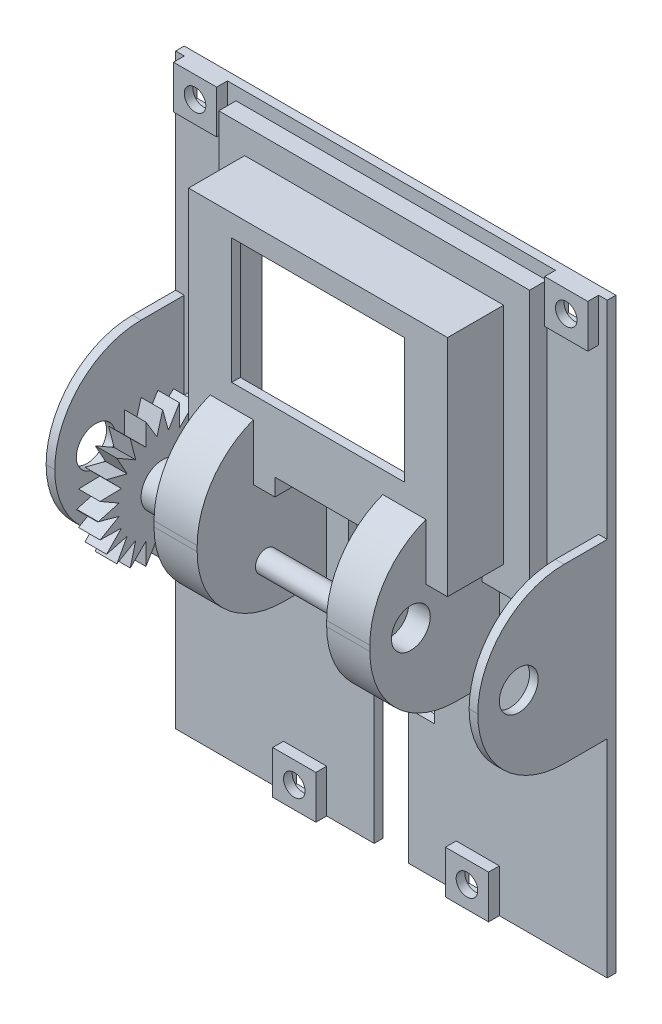
SolidWorks part; units mm, degrees
material "ABS"
ref_plane "Plan de face" through (0, 0, 0) normal (0, 0, 1) x (1, 0, 0)
ref_plane "Plan de dessus" through (0, 0, 0) normal (0, 1, 0) x (1, 0, 0)
ref_plane "Plan de droite" through (0, 0, 0) normal (1, 0, 0) x (0, 0, -1)
sketch "Esquisse1" plane through (0, 0, 0) normal (0, 0, 1) x (1, 0, 0)
  line L0 (0, 0) -> (0, 87) construction
  line L1 (-50, -68) -> (50, -68)
  line L2 (-50, -68) -> (-50, 68)
  line L3 (-50, 68) -> (50, 68)
  line L4 (50, -68) -> (50, 68)
  line L5 (-50, -68) -> (50, 68) construction
  line L6 (-50, 68) -> (50, -68) construction
  line L7 (-34, 3) -> (34, 3)
  line L8 (-34, 3) -> (-34, 63)
  line L9 (-34, 63) -> (34, 63)
  line L10 (34, 3) -> (34, 63)
  line L11 (0, 87) -> (0, -87) construction
  line L13 (-10, 3) -> (10, 3)
  line L14 (-10, 3) -> (-10, -37)
  line L15 (-10, -68) -> (10, -68)
  line L16 (10, 3) -> (10, -37)
  line L17 (-10, 3) -> (10, 3)
  line L18 (-10, 3) -> (-10, -37)
  line L19 (-10, -37) -> (10, -37)
  line L20 (10, 3) -> (10, -37)
  point P0 (0, 0)
  dimension "D1" = 136
  dimension "D2" = 100
  dimension "D3" = 68
  dimension "D4" = 60
  dimension "D5" = 16
  dimension "D6" = 5
  dimension "D7" = 174
  dimension "D8" = 87
  dimension "D9" = 20
  dimension "D10" = 24
  dimension "D11" = 40
extrude "Boss.-Extru.1" add sketch "Esquisse1" along normal blind 2 contours L1 L4 L3 L2 L19 L14 L7 L8 L9 L10 L16 region at (-48.3119, 0, 0)
sketch "Esquisse2" plane through (0, 0, 2) normal (0, 0, 1) x (1, 0, 0)
  line L0 (-34, 63) -> (34, 63) construction
  line L1 (-36, 65) -> (36, 65)
  line L2 (-36, 65) -> (-36, 1)
  line L3 (-36, 1) -> (36, 1)
  line L4 (36, 65) -> (36, 1)
  line L5 (-34, 3) -> (-34, 63) construction
  line L6 (34, 3) -> (34, 63) construction
  line L7 (10, 3) -> (34, 3) construction
  line L9 (-34, 63) -> (34, 63)
  line L10 (-34, 63) -> (-34, 3)
  line L11 (-34, 3) -> (34, 3)
  line L12 (34, 63) -> (34, 3)
  line L13 (-10, 3) -> (10, 3)
  line L14 (-10, 3) -> (-10, 1)
  line L15 (-10, 1) -> (10, 1)
  line L16 (10, 3) -> (10, 1)
  line M6 (-10, -37) -> (-10, 3)
  line M7 (-10, 3) -> (-34, 3)
  line M8 (-34, 3) -> (-34, 63)
  line M9 (-34, 63) -> (34, 63)
  line M10 (34, 63) -> (34, 3)
  line M11 (34, 3) -> (10, 3)
  line M12 (10, 3) -> (10, -37)
  dimension "D1" = 2
  dimension "D2" = 2
  dimension "D3" = 2
  dimension "D4" = 2
  dimension "D5" = 20
extrude "Boss.-Extru.2" add sketch "Esquisse2" along normal blind 4 contours L4 L1 L2 L3 M6 M7 M8 M9 M10 M11 M12 region at (0, 64.0367, 2)
sketch "Esquisse3" plane through (0, 0, 6) normal (0, 0, 1) x (1, 0, 0)
  line L1 (-34, 63) -> (34, 63)
  line L2 (-34, 63) -> (-34, 3)
  line L3 (-34, 3) -> (34, 3)
  line L4 (34, 63) -> (34, 3)
  line L5 (-28, 57) -> (28, 57)
  line L6 (-28, 57) -> (-28, 9)
  line L7 (-28, 9) -> (28, 9)
  line L8 (28, 57) -> (28, 9)
  dimension "D1" = 6
  dimension "D2" = 6
  dimension "D3" = 6
  dimension "D4" = 6
extrude "Boss.-Extru.3" add sketch "Esquisse3" against normal blind 2
sketch "Esquisse4" plane through (0, 0, 6) normal (0, 0, 1) x (1, 0, 0)
  line L1 (-28, 57) -> (28, 57)
  line L2 (-28, 57) -> (-28, 9)
  line L3 (-28, 9) -> (28, 9)
  line L4 (28, 57) -> (28, 9)
  line L5 (-30, 59) -> (30, 59)
  line L6 (-30, 59) -> (-30, 7)
  line L7 (-30, 7) -> (30, 7)
  line L8 (30, 59) -> (30, 7)
  dimension "D1" = 2
  dimension "D2" = 2
  dimension "D3" = 2
  dimension "D4" = 2
extrude "Boss.-Extru.4" add sketch "Esquisse4" along normal blind 13
sketch "Esquisse5" plane through (0, 0, 19) normal (0, 0, 1) x (1, 0, 0)
  line L1 (-28, 57) -> (28, 57)
  line L2 (-28, 57) -> (-28, 9)
  line L3 (-28, 9) -> (28, 9)
  line L4 (28, 57) -> (28, 9)
extrude "Boss.-Extru.5" add sketch "Esquisse5" against normal blind 2
sketch "Esquisse6" plane through (0, 0, 19) normal (0, 0, 1) x (1, 0, 0)
  line L1 (-10, 1) -> (10, 1)
  line L2 (-10, 1) -> (-10, 11)
  line L3 (-10, 11) -> (10, 11)
  line L4 (10, 1) -> (10, 11)
  dimension "D1" = 20
  dimension "D2" = 10
extrude "Enlèv. mat.-Extru.1" cut sketch "Esquisse6" against normal blind 35
sketch "Esquisse9" plane through (0, 0, 2) normal (0, 0, 1) x (1, 0, 0)
  line L0 (0, 0) -> (50, 0) construction
  line L1 (50, -68) -> (50, 68) construction
  line L2 (50, 0) -> (-50, 0) construction
  line L3 (-50, -68) -> (-50, 68) construction
  line L4 (-36, 1) -> (-10, 1) construction
  line L5 (-50, 20) -> (-48, 20)
  line L6 (-50, 20) -> (-50, -20)
  line L7 (-50, -20) -> (-48, -20)
  line L8 (-48, 20) -> (-48, -20)
  line L9 (50, 20) -> (48, 20)
  line L10 (50, 20) -> (50, -20)
  line L11 (50, -20) -> (48, -20)
  line L12 (48, 20) -> (48, -20)
  line L13 (-25, -20) -> (-15, -20)
  line L14 (-25, -20) -> (-25, 1)
  line L15 (-25, 1) -> (-15, 1)
  line L16 (-15, -20) -> (-15, 1)
  line L17 (10, 1) -> (36, 1) construction
  line L18 (15, 1) -> (25, 1)
  line L19 (15, 1) -> (15, -20)
  line L20 (15, -20) -> (25, -20)
  line L21 (25, 1) -> (25, -20)
  line L22 (-10, 1) -> (-10, -37) construction
  line L23 (10, 1) -> (10, -37) construction
  dimension "D1" = 2
  dimension "D2" = 40
  dimension "D3" = 20
  dimension "D4" = 40
  dimension "D5" = 2
  dimension "D6" = 20
  dimension "D7" = 10
  dimension "D8" = 10
  dimension "D9" = 21
  dimension "D10" = 21
  dimension "D11" = 5
  dimension "D12" = 5
extrude "Boss.-Extru.9" add sketch "Esquisse9" along normal blind 30
fillet "Congé5" radius 20 4 edges at (49, -20, 32) (49, 20, 32) (-49, -20, 32) (-49, 20, 32)
sketch "Esquisse10" plane through (0, 0, 6) normal (0, 0, 1) x (1, 0, 0)
  line L0 (-30, 7) -> (-10, 7) construction
  line L1 (-25, 1) -> (-15, 1)
  line L2 (-25, 1) -> (-25, 7)
  line L3 (-25, 7) -> (-15, 7)
  line L4 (-15, 1) -> (-15, 7)
  line L5 (10, 7) -> (30, 7) construction
  line L6 (15, 1) -> (25, 1)
  line L7 (15, 1) -> (15, 7)
  line L8 (15, 7) -> (25, 7)
  line L9 (25, 1) -> (25, 7)
  dimension "D1" = 10
  dimension "D2" = 10
extrude "Boss.-Extru.10" add sketch "Esquisse10" along normal blind 26
sketch "Esquisse11" plane through (0, 0, 19) normal (0, 0, 1) x (1, 0, 0)
  line L1 (-25, 7) -> (-15, 7)
  line L2 (-25, 7) -> (-25, 20)
  line L3 (-25, 20) -> (-15, 20)
  line L4 (-15, 7) -> (-15, 20)
  line L5 (15, 7) -> (25, 7)
  line L6 (15, 7) -> (15, 20)
  line L7 (15, 20) -> (25, 20)
  line L8 (25, 7) -> (25, 20)
  dimension "D1" = 13
  dimension "D2" = 13
  dimension "D3" = 10
  dimension "D4" = 10
extrude "Boss.-Extru.11" add sketch "Esquisse11" along normal blind 13
fillet "Congé6" radius 20 2 edges at (20, 20, 32) (-20, 20, 32)
fillet "Congé7" radius 20 2 edges at (20, -20, 32) (-20, -20, 32)
sketch "Esquisse12" plane through (-15, 0, 0) normal (1, 0, 0) x (0, 0, -1)
  line L0 (0, 0) -> (-32, 0) construction
  line L1 (-16, 0) -> (-16, -19.5959) construction
  line L2 (-16, 0) -> (-16, -9.798) construction
  arc A0 (-32, 0) -> (-12, -20) centre (-12, 0) ccw construction
  circle A1 centre (-16, -9.798) radius 2.5
  dimension "D1" = 5
extrude "Boss.-Extru.12" add sketch "Esquisse12" along normal blind 36
sketch "Esquisse13" plane through (50, 0, 0) normal (1, 0, 0) x (0, 0, -1)
  line L0 (0, 0) -> (-32, 0) construction
  line L1 (-32, 0) -> (-27, 0) construction
  arc A0 (-32, 0) -> (-12, -20) centre (-12, 0) ccw construction
  circle A1 centre (-22.5, 0) radius 4.5
  dimension "D2" = 9
  dimension "D1" = 5
extrude "Enlèv. mat.-Extru.2" cut sketch "Esquisse13" against normal blind 30
sketch "Esquisse14" plane through (-50, 0, 0) normal (-1, 0, 0) x (0, 0, 1)
  line L0 (0, 0) -> (32, 0) construction
  line L1 (32, 0) -> (27, 0) construction
  circle A0 centre (22.5, 0) radius 4.5
  dimension "D2" = 9
  dimension "D1" = 5
extrude "Enlèv. mat.-Extru.4" cut sketch "Esquisse14" against normal blind 17
sketch "Esquisse15" plane through (-25, 0, 0) normal (-1, 0, 0) x (0, 0, 1)
  line L0 (0, 0) -> (32, 0) construction
  line L1 (32, 0) -> (27.5, 0) construction
  circle A0 centre (22.5, 0) radius 5
  dimension "D2" = 10
  dimension "D1" = 4.5
extrude "Boss.-Extru.13" add sketch "Esquisse15" along normal blind 12.5
sketch "Esquisse16" plane through (0, 0, 2) normal (0, 0, 1) x (1, 0, 0)
  line L0 (-47.5, 0) -> (47.5, 0) construction
  line L1 (-47.5, 0) -> (-38, 0) construction
  line L2 (-38, 0) -> (-37.5, 0) construction
  line L4 (-37.5, 0) -> (-36.5, 0)
  line L5 (-37.5, 0) -> (-37.5, 1)
  line L6 (-37.5, 1) -> (-36.5, 1)
  line L7 (-36.5, 0) -> (-36.5, 1)
  line L8 (-37.5, 0) -> (-36.5, 0)
  line L9 (-37.5, 0) -> (-37.5, -1)
  line L10 (-37.5, -1) -> (-36.5, -1)
  line L11 (-36.5, 0) -> (-36.5, -1)
  dimension "D1" = 95
  dimension "D2" = 2.5
  dimension "D3" = 9.5
  dimension "D4" = 0.5
  dimension "D5" = 1
  dimension "D6" = 1
  dimension "D7" = 1
extrude "Boss.-Extru.14" add sketch "Esquisse16" along normal blind 2 contours L4 L7 L6 L5 | L11 L4 L9 L10 region at (-37, 0.5, 2) region at (-37, -0.5, 2)
sketch "Esquisse17" plane through (-37.5, 0, 0) normal (-1, 0, 0) x (0, 0, 1)
  line L0 (22.5, 5) -> (22.5, -5) construction
  line L1 (0, 0) -> (22.5, 0) construction
  circle A0 centre (22.5, 0) radius 5 construction
  circle A1 centre (22.5, 0) radius 5 construction
  circle A2 centre (22.5, 0) radius 15
  dimension "D1" = 30
extrude "Boss.-Extru.16" add sketch "Esquisse17" against normal blind 5
sketch "Esquisse18" plane through (-50, 0, 0) normal (-1, 0, 0) x (0, 0, 1)
  circle A0 centre (22.5, 0) radius 4.5
extrude "Enlèv. mat.-Extru.5" cut sketch "Esquisse18" against normal blind 16
sketch "Esquisse23" plane through (-37.5, 0, 0) normal (-1, 0, 0) x (0, 0, 1)
  line L0 (22.5, 0) -> (22.5, 15) construction
  line L1 (22.5, 15) -> (22.5, -15) construction
  line L2 (22.5, 0) -> (7.5, 0) construction
  line L3 (7.5, 0) -> (37.5, 0) construction
  line L4 (22.5, 15) -> (23.92, 9.8987)
  line L5 (22.5, 15) -> (21.07, 9.8972)
  line L6 (21.3706, 9.936) -> (18.6136, 14.4878)
  line L7 (18.6136, 14.4878) -> (18.6136, 9.2139)
  line L8 (22.5, 0) -> (18.6136, 14.4878) construction
  line L9 (22.5, 0) -> (14.9926, 12.9861) construction
  line L10 (22.5, 0) -> (11.8844, 10.5976) construction
  line L11 (22.5, 0) -> (9.5011, 7.4853) construction
  line L12 (22.5, 0) -> (8.0056, 3.8618) construction
  line L13 (11.8844, 10.5976) -> (16.4547, 7.9658)
  line L14 (14.4531, 5.937) -> (11.8844, 10.5976)
  line L15 (9.5011, 7.4853) -> (13.2133, 3.7091)
  line L16 (9.5011, 7.4853) -> (14.6367, 6.1781)
  line L17 (14.9926, 12.9861) -> (18.7752, 9.2804)
  line L18 (14.9926, 12.9861) -> (16.3085, 7.8527)
  line L19 (13.3259, 3.9795) -> (8.0056, 3.8618)
  line L20 (8.0056, 3.8618) -> (12.5759, 1.23)
  line L21 (7.5, -0.0255) -> (12.6004, 1.4132)
  line L22 (7.5, -0.0255) -> (12.6038, -1.4368)
  line L23 (37.5, -0.0255) -> (32.3996, 1.4132)
  line L24 (35.4989, 7.4853) -> (31.7867, 3.7091)
  line L25 (36.9944, 3.8618) -> (32.4241, 1.23)
  line L26 (31.6741, 3.9795) -> (36.9944, 3.8618)
  line L27 (35.4989, 7.4853) -> (30.3633, 6.1781)
  line L28 (30.5469, 5.937) -> (33.1156, 10.5976)
  line L29 (33.1156, 10.5976) -> (28.5453, 7.9658)
  line L30 (30.0074, 12.9861) -> (28.6915, 7.8527)
  line L31 (30.0074, 12.9861) -> (26.2248, 9.2804)
  line L32 (26.3864, 14.4878) -> (26.3864, 9.2139)
  line L33 (23.6294, 9.936) -> (26.3864, 14.4878)
  line L34 (22.5, 15) -> (23.93, 9.8972)
  line L35 (37.5, 0.0255) -> (32.3996, -1.4132)
  line L36 (36.9944, -3.8618) -> (32.4241, -1.23)
  line L37 (31.6741, -3.9795) -> (36.9944, -3.8618)
  line L38 (35.4989, -7.4853) -> (31.7867, -3.7091)
  line L39 (35.4989, -7.4853) -> (30.3633, -6.1781)
  line L40 (30.5469, -5.937) -> (33.1156, -10.5976)
  line L41 (33.1156, -10.5976) -> (28.5453, -7.9658)
  line L42 (30.0074, -12.9861) -> (28.6915, -7.8527)
  line L43 (30.0074, -12.9861) -> (26.2248, -9.2804)
  line L44 (26.3864, -14.4878) -> (26.3864, -9.2139)
  line L45 (23.6294, -9.936) -> (26.3864, -14.4878)
  line L46 (22.5, -15) -> (23.92, -9.8987)
  line L47 (22.5, -15) -> (21.07, -9.8972)
  line L48 (21.3706, -9.936) -> (18.6136, -14.4878)
  line L49 (18.6136, -14.4878) -> (18.6136, -9.2139)
  line L50 (14.9926, -12.9861) -> (18.7752, -9.2804)
  line L51 (14.9926, -12.9861) -> (16.3085, -7.8527)
  line L52 (11.8844, -10.5976) -> (16.4547, -7.9658)
  line L53 (14.4531, -5.937) -> (11.8844, -10.5976)
  line L54 (9.5011, -7.4853) -> (14.6367, -6.1781)
  line L55 (9.5011, -7.4853) -> (13.2133, -3.7091)
  line L56 (13.3259, -3.9795) -> (8.0056, -3.8618)
  line L57 (8.0056, -3.8618) -> (12.5759, -1.23)
  line L58 (7.5, 0.0255) -> (12.6004, -1.4132)
  circle A0 centre (22.5, 0) radius 15 construction
  circle A1 centre (22.5, 0) radius 15
  circle A2 centre (22.5, 0) radius 10
  circle M34 centre (22.5, 0) radius 15
  dimension "D2" = 20
  dimension "D7" = 3.92
  dimension "D8" = 2.85
  dimension "D9" = 1.42
  dimension "D10" = 2.85
extrude "Enlèv. mat.-Extru.7" cut sketch "Esquisse23" against normal blind 5 contours L18 L13 M34 | L17 L7 M34 | L6 L5 M34 | L34 L33 M34 | L32 L31 M34 | L30 L29 M34 | L24 L26 M34 | L28 L27 M34 | L35 L25 L23 M34 | L36 L23 L35 M34 | L38 L37 M34 | L39 L40 M34 | L42 L41 M34 | L44 L43 M34 | L46 L45 M34 | L47 L48 M34 | L50 L49 M34 | L52 L51 M34 | L54 L53 M34 | L55 L56 M34 | L57 L22 M34 | L58 L21 L20 M34 | L19 L15 M34 | L16 L14 M34 region at (-37.5, 13.3067, 24.2457) region at (-37.5, 13.3067, 20.7543) region at (-37.5, 12.3567, 27.6155) region at (-37.5, 12.3567, 17.3845) region at (-37.5, 10.6014, 30.659) region at (-37.5, 10.6014, 14.341) region at (-37.5, 8.1531, 33.1604) region at (-37.5, 8.1531, 11.8396) region at (-37.5, 5.1275, 34.8988) region at (-37.5, 5.1275, 10.1012) region at (-37.5, 1.7356, 35.7641) region at (-37.5, 1.7356, 9.2359) region at (-37.5, -1.7356, 35.7641) region at (-37.5, -1.7576, 9.2275) region at (-37.5, -5.1275, 10.1012) region at (-37.5, -5.1275, 34.8988) region at (-37.5, -8.1531, 11.8396) region at (-37.5, -8.1531, 33.1604) region at (-37.5, -10.6014, 14.341) region at (-37.5, -10.6014, 30.659) region at (-37.5, -12.3567, 17.3845) region at (-37.5, -12.3567, 27.6155) region at (-37.5, -13.3067, 20.7543) region at (-37.5, -13.3034, 24.2437)
sketch "Esquisse24" plane through (0, 0, 19) normal (0, 0, 1) x (1, 0, 0)
  line L0 (30, 59) -> (-30, 59) construction
  line L1 (-20, 54) -> (20, 54)
  line L2 (-20, 54) -> (-20, 25)
  line L3 (-20, 25) -> (20, 25)
  line L4 (20, 54) -> (20, 25)
  line L5 (-30, 59) -> (-30, 7) construction
  line L6 (30, 7) -> (30, 59) construction
  line L7 (-15, 20) -> (-25, 20) construction
  dimension "D1" = 5
  dimension "D2" = 10
  dimension "D3" = 10
  dimension "D4" = 5
extrude "Enlèv. mat.-Extru.8" cut sketch "Esquisse24" against normal blind 10
sketch "Esquisse25" plane through (0, 0, 2) normal (0, 0, 1) x (1, 0, 0)
  line L10 (-50, 63) -> (-36, 63) construction
  line L11 (-43, 58) -> (-43, 68) construction
  line L12 (36, 63) -> (50, 63) construction
  line L13 (43, 58) -> (43, 68) construction
  circle A0 centre (-43, 63) radius 2.5
  circle A1 centre (43, 63) radius 2.5
  dimension "D3" = 5
  dimension "D4" = 5
extrude "Enlèv. mat.-Extru.9" cut sketch "Esquisse25" against normal blind 10
sketch "Esquisse26" plane through (0, 0, 2) normal (0, 0, 1) x (1, 0, 0)
  line L0 (0, 0) -> (0, -68) construction
  line L1 (-50, -68) -> (50, -68) construction
  line L2 (-10, -37) -> (10, -37) construction
  line L3 (-4, -37) -> (4, -37)
  line L4 (-4, -37) -> (-4, -68)
  line L5 (-4, -68) -> (4, -68)
  line L6 (4, -37) -> (4, -68)
  dimension "D1" = 8
  dimension "D2" = 4
extrude "Enlèv. mat.-Extru.10" cut sketch "Esquisse26" against normal blind 10
sketch "Esquisse27" plane through (0, 0, 0) normal (0, 0, -1) x (-1, 0, 0)
  line L0 (-50, -68) -> (50, -68) construction
  line L1 (0, 0) -> (0, -68) construction
  line L2 (-25, -68) -> (-25, -58) construction
  line L3 (-25, -58) -> (25, -58) construction
  line L4 (25, -58) -> (25, -68) construction
  line L5 (-15, -58) -> (-15, -68) construction
  line L6 (-24, -59) -> (-16, -59)
  line L7 (-24, -59) -> (-24, -67)
  line L8 (-24, -67) -> (-16, -67)
  line L9 (-16, -59) -> (-16, -67)
  line L10 (24, -67) -> (16, -67)
  line L11 (16, -59) -> (16, -67)
  line L12 (24, -59) -> (16, -59)
  line L13 (24, -59) -> (24, -67)
  dimension "D1" = 10
  dimension "D2" = 50
  dimension "D3" = 25
  dimension "D4" = 8
  dimension "D5" = 8
  dimension "D6" = 1
  dimension "D7" = 1
  dimension "D8" = 1
extrude "Enlèv. mat.-Extru.11" cut sketch "Esquisse27" against normal blind 2.5
sketch "Esquisse28" plane through (0, 0, 2) normal (0, 0, 1) x (1, 0, 0)
  line L0 (-50, -68) -> (-4, -68) construction
  line L1 (-25, -58) -> (-15, -58)
  line L2 (-25, -58) -> (-25, -68)
  line L3 (-25, -68) -> (-15, -68)
  line L4 (-15, -58) -> (-15, -68)
  line L5 (0, 0) -> (0, -68) construction
  line L6 (-24, -59) -> (-16, -59)
  line L7 (-24, -59) -> (-24, -67)
  line L8 (-24, -67) -> (-16, -67)
  line L9 (-16, -59) -> (-16, -67)
  line L10 (-50, -68) -> (50, -68) construction
  line L11 (25, -68) -> (15, -68)
  line L12 (15, -58) -> (15, -68)
  line L13 (25, -58) -> (15, -58)
  line L14 (25, -58) -> (25, -68)
  line L15 (24, -67) -> (16, -67)
  line L16 (16, -59) -> (16, -67)
  line L17 (24, -59) -> (16, -59)
  line L18 (24, -59) -> (24, -67)
  dimension "D1" = 1
  dimension "D2" = 1
  dimension "D3" = 1
extrude "Boss.-Extru.17" add sketch "Esquisse28" along normal blind 2.5
sketch "Esquisse29" plane through (0, 0, 4.5) normal (0, 0, 1) x (1, 0, 0)
  line L0 (0, 0) -> (0, -67) construction
  line L1 (-24, -59) -> (-16, -59)
  line L2 (-24, -59) -> (-24, -67)
  line L3 (-24, -67) -> (-16, -67)
  line L4 (-16, -59) -> (-16, -67)
  line L5 (24, -67) -> (16, -67)
  line L6 (16, -59) -> (16, -67)
  line L7 (24, -59) -> (16, -59)
  line L8 (24, -59) -> (24, -67)
extrude "Boss.-Extru.18" add sketch "Esquisse29" against normal blind 2
sketch "Esquisse30" plane through (0, 0, 4.5) normal (0, 0, 1) x (1, 0, 0)
  line L0 (-25, -63) -> (-15, -63) construction
  line L1 (-25, -58) -> (-25, -68) construction
  line L2 (-15, -68) -> (-15, -58) construction
  line L3 (-20, -58) -> (-20, -68) construction
  line L4 (-15, -58) -> (-25, -58) construction
  line L5 (-25, -68) -> (-15, -68) construction
  line L6 (0, 0) -> (0, -70.7029) construction
  circle A0 centre (-20, -63) radius 2.5
  circle A1 centre (20, -63) radius 2.5
  dimension "D1" = 5
extrude "Enlèv. mat.-Extru.12" cut sketch "Esquisse30" against normal blind 2 contours A0 | A1
sketch "Esquisse31" plane through (0, 0, 0) normal (0, 0, -1) x (-1, 0, 0)
  line L0 (0, 0) -> (0, 68) construction
  line L1 (-47, 59) -> (-39, 59)
  line L2 (-47, 59) -> (-47, 67)
  line L3 (-47, 67) -> (-39, 67)
  line L4 (-39, 59) -> (-39, 67)
  line L5 (-47, 59) -> (-39, 67) construction
  line L6 (-47, 67) -> (-39, 59) construction
  line L7 (50, 68) -> (-50, 68) construction
  line L8 (47, 67) -> (39, 67)
  line L9 (39, 59) -> (39, 67)
  line L10 (47, 59) -> (39, 59)
  line L11 (47, 59) -> (47, 67)
  point P0 (-43, 63)
  dimension "D1" = 8
  dimension "D2" = 8
extrude "Enlèv. mat.-Extru.13" cut sketch "Esquisse31" against normal blind 2.5
sketch "Esquisse32" plane through (0, 0, 2) normal (0, 0, 1) x (1, 0, 0)
  line L0 (0, 0) -> (0, 68) construction
  line L1 (-50, 68) -> (50, 68) construction
  line L2 (48, 68) -> (38, 68)
  line L3 (-47, 59) -> (-39, 59)
  line L4 (-47, 59) -> (-47, 67)
  line L5 (-47, 67) -> (-39, 67)
  line L6 (-39, 59) -> (-39, 67)
  line L7 (-48, 58) -> (-38, 58)
  line L8 (-48, 58) -> (-48, 68)
  line L9 (-48, 68) -> (-38, 68)
  line L10 (-38, 58) -> (-38, 68)
  line L11 (38, 58) -> (38, 68)
  line L12 (48, 58) -> (38, 58)
  line L13 (48, 58) -> (48, 68)
  line L14 (47, 67) -> (39, 67)
  line L15 (39, 59) -> (39, 67)
  line L16 (47, 59) -> (39, 59)
  line L17 (47, 59) -> (47, 67)
  dimension "D1" = 1
  dimension "D2" = 1
  dimension "D3" = 1
extrude "Boss.-Extru.19" add sketch "Esquisse32" along normal blind 2.5
sketch "Esquisse33" plane through (0, 0, 4.5) normal (0, 0, 1) x (1, 0, 0)
  line L0 (0, 0) -> (0, 68) construction
  line L1 (-47, 67) -> (-39, 67)
  line L2 (-47, 67) -> (-47, 59)
  line L3 (-47, 59) -> (-39, 59)
  line L4 (-39, 67) -> (-39, 59)
  line L5 (-38, 68) -> (38, 68) construction
  line L6 (47, 67) -> (47, 59)
  line L7 (47, 59) -> (39, 59)
  line L8 (39, 67) -> (39, 59)
  line L9 (47, 67) -> (39, 67)
extrude "Boss.-Extru.20" add sketch "Esquisse33" against normal blind 2
sketch "Esquisse34" plane through (0, 0, 4.5) normal (0, 0, 1) x (1, 0, 0)
  line L0 (-38, 68) -> (-48, 68) construction
  line L1 (-48, 68) -> (-48, 58) construction
  line L2 (48, 58) -> (48, 68) construction
  line L3 (48, 68) -> (38, 68) construction
  circle A0 centre (-43, 63) radius 2.5
  circle A1 centre (43, 63) radius 2.5
  dimension "D1" = 5
  dimension "D4" = 5
  dimension "D2" = 5
  dimension "D3" = 5
  dimension "D5" = 5
  dimension "D6" = 5
extrude "Enlèv. mat.-Extru.14" cut sketch "Esquisse34" against normal blind 2
